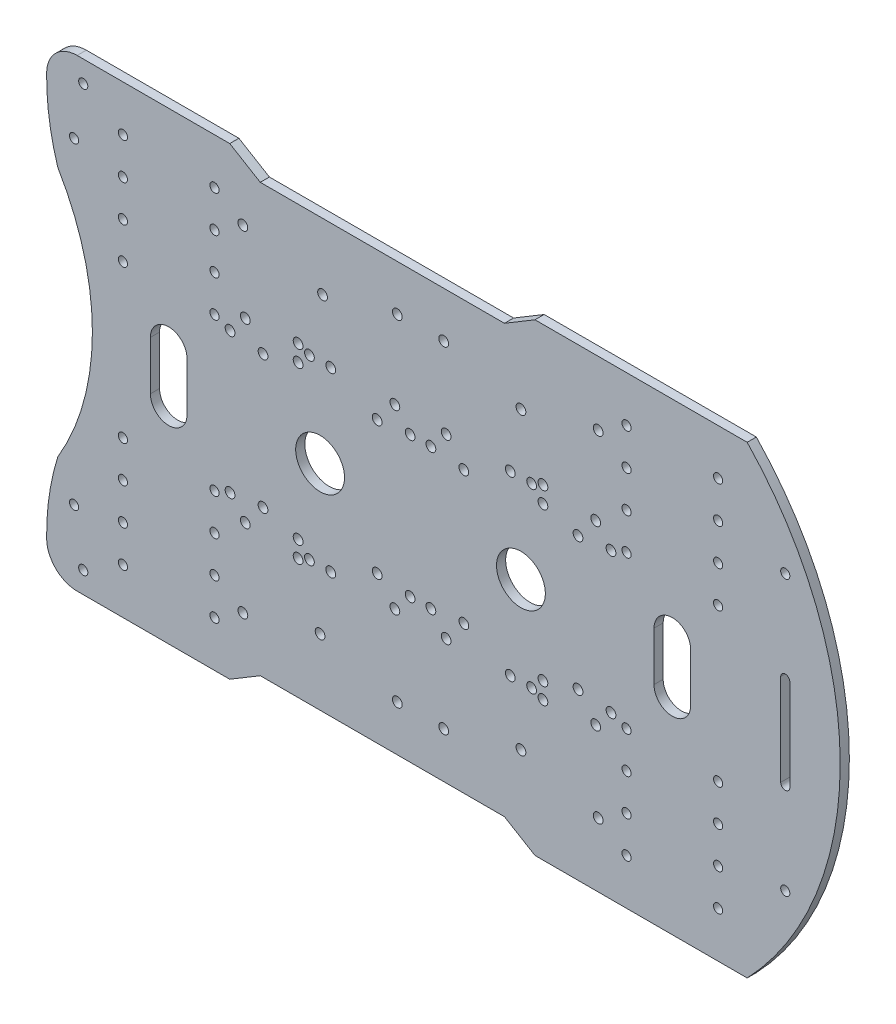
SolidWorks part; units mm, degrees
ref_plane "Front Plane" through (0, 0, 0) normal (0, 0, 1) x (1, 0, 0)
ref_plane "Top Plane" through (0, 0, 0) normal (0, 1, 0) x (1, 0, 0)
ref_plane "Right Plane" through (0, 0, 0) normal (1, 0, 0) x (0, 0, -1)
sketch "Model" plane through (0, 0, 0) normal (0, 0, 1) x (1, 0, 0)
  line L0 (404, 14.25) -> (584, 14.25)
  line L1 (584, 48.25) -> (404, 48.25)
  line L2 (404, 65.25) -> (584, 65.25)
  line L3 (430.991, 48.25) -> (430.991, 10)
  line L4 (502.8, 31.25) -> (404, 31.25)
  line L5 (502.8, 35.5) -> (404, 35.5)
  line L6 (502.8, 39.75) -> (404, 39.75)
  line L7 (502.8, 44) -> (404, 44)
  line L8 (458.6, 10) -> (458.6, 48.25)
  line L9 (404, 65.25) -> (404, 10)
  line L10 (411.8, 48.25) -> (411.8, 10)
  line L11 (437.8, 48.25) -> (437.8, 65.25)
  line L12 (448.3989, 48.25) -> (448.3989, 10)
  line L13 (469, 31.25) -> (469, 48.25)
  line L14 (458.6, 18.5) -> (404, 18.5)
  line L15 (484.6, 65.25) -> (484.6, 27)
  line L16 (458.6, 22.7499) -> (404, 22.7499)
  line L17 (458.6, 27) -> (404, 27)
  line L18 (458.6, 27) -> (584, 27)
  line L19 (502.8, 65.25) -> (502.8, 10)
  line L20 (547, 10) -> (547, 14.25)
  line L21 (554.8, 58.875) -> (554.8, 65.25)
  line L22 (571, 14.25) -> (571, 27)
  line L23 (584, 58.875) -> (502.8, 58.875)
  line L24 (584, 18.5) -> (571, 18.5)
  line L25 (20, 10) -> (20, 410)
  line L26 (20, 410) -> (584, 410)
  line L27 (584, 410) -> (584, 10)
  line L28 (584, 10) -> (20, 10)
  line L29 (15, 5) -> (15, 415)
  line L30 (15, 415) -> (589, 415)
  line L31 (589, 415) -> (589, 5)
  line L32 (589, 5) -> (15, 5)
  line L33 (15, 210) -> (25, 210)
  line L34 (302, 415) -> (302, 405)
  line L35 (589, 210) -> (579, 210)
  line L36 (302, 5) -> (302, 15)
  line L37 (20, 60) -> (15, 60)
  line L38 (584, 60) -> (589, 60)
  line L39 (20, 110) -> (15, 110)
  line L40 (584, 110) -> (589, 110)
  line L41 (20, 160) -> (15, 160)
  line L42 (584, 160) -> (589, 160)
  line L43 (20, 210) -> (15, 210)
  line L44 (584, 210) -> (589, 210)
  line L45 (20, 260) -> (15, 260)
  line L46 (584, 260) -> (589, 260)
  line L47 (20, 310) -> (15, 310)
  line L48 (584, 310) -> (589, 310)
  line L49 (20, 360) -> (15, 360)
  line L50 (584, 360) -> (589, 360)
  line L51 (52, 410) -> (52, 415)
  line L52 (52, 10) -> (52, 5)
  line L53 (102, 410) -> (102, 415)
  line L54 (102, 10) -> (102, 5)
  line L55 (152, 410) -> (152, 415)
  line L56 (152, 10) -> (152, 5)
  line L57 (202, 410) -> (202, 415)
  line L58 (202, 10) -> (202, 5)
  line L59 (252, 410) -> (252, 415)
  line L60 (252, 10) -> (252, 5)
  line L61 (302, 410) -> (302, 415)
  line L62 (302, 10) -> (302, 5)
  line L63 (352, 410) -> (352, 415)
  line L64 (352, 10) -> (352, 5)
  line L65 (402, 410) -> (402, 415)
  line L66 (402, 10) -> (402, 5)
  line L67 (452, 410) -> (452, 415)
  line L68 (452, 10) -> (452, 5)
  line L69 (502, 410) -> (502, 415)
  line L70 (502, 10) -> (502, 5)
  line L71 (552, 410) -> (552, 415)
  line L72 (552, 10) -> (552, 5)
  line L73 (307.6913, 297.7528) -> (307.6913, 281.7528)
  line L74 (319.6913, 297.7528) -> (319.6913, 281.7528)
  line L75 (349.1913, 304.7528) -> (349.1913, 274.7528)
  line L76 (352.1913, 304.7528) -> (352.1913, 274.7528)
  line L77 (142.6913, 297.7528) -> (142.6913, 281.7528)
  line L78 (154.6913, 297.7528) -> (154.6913, 281.7528)
  line L79 (118.6985, 365.7528) -> (168.6913, 365.7528)
  line L80 (168.6913, 365.7528) -> (178.6913, 359.7528)
  line L81 (178.6913, 359.7528) -> (258.6913, 359.7528)
  line L82 (258.6913, 359.7528) -> (268.6913, 365.7528)
  line L83 (268.6913, 365.7528) -> (338.2149, 365.7528)
  line L84 (268.6913, 213.7528) -> (338.2149, 213.7528)
  line L85 (258.6913, 219.7528) -> (268.6913, 213.7528)
  line L86 (178.6913, 219.7528) -> (258.6913, 219.7528)
  line L87 (168.6913, 213.7528) -> (178.6913, 219.7528)
  line L88 (118.6985, 213.7528) -> (168.6913, 213.7528)
  line L89 (473.3173, 213.7528) -> (473.3173, 365.7528)
  line L90 (473.3173, 365.7528) -> (476.3173, 365.7528)
  line L91 (473.3173, 213.7528) -> (476.3173, 213.7528)
  line L92 (476.3173, 365.7528) -> (476.3173, 213.7528)
  circle A0 centre (328.6913, 264.7528) radius 1.5
  circle A1 centre (298.6913, 252.7528) radius 1.5
  circle A2 centre (298.6913, 240.7528) radius 1.5
  circle A3 centre (298.6913, 228.7528) radius 1.5
  arc A4 (319.6913, 297.7528) -> (307.6913, 297.7528) centre (313.6913, 297.7528) ccw
  arc A5 (352.1913, 304.7528) -> (349.1913, 304.7528) centre (350.6913, 304.7528) ccw
  circle A6 centre (163.6913, 264.7528) radius 1.5
  circle A7 centre (163.6913, 252.7528) radius 1.5
  circle A8 centre (163.6913, 240.7528) radius 1.5
  circle A9 centre (163.6913, 228.7528) radius 1.5
  circle A10 centre (120.6913, 220.7528) radius 1.5
  arc A11 (154.6913, 297.7528) -> (142.6913, 297.7528) centre (148.6913, 297.7528) ccw
  circle A12 centre (163.6913, 314.7528) radius 1.5
  circle A13 centre (133.6913, 314.7528) radius 1.5
  circle A14 centre (163.6913, 326.7528) radius 1.5
  circle A15 centre (133.6913, 326.7528) radius 1.5
  circle A16 centre (163.6913, 338.7528) radius 1.5
  circle A17 centre (133.6913, 338.7528) radius 1.5
  circle A18 centre (163.6913, 350.7528) radius 1.5
  circle A19 centre (133.6913, 350.7528) radius 1.5
  circle A20 centre (120.6913, 358.7528) radius 1.5
  circle A21 centre (117.6913, 341.7528) radius 1.5
  circle A22 centre (298.6913, 314.7528) radius 1.5
  circle A23 centre (328.6913, 314.7528) radius 1.5
  circle A24 centre (328.6913, 326.7528) radius 1.5
  circle A25 centre (298.6913, 326.7528) radius 1.5
  circle A26 centre (328.6913, 338.7528) radius 1.5
  circle A27 centre (298.6913, 338.7528) radius 1.5
  circle A28 centre (328.6913, 350.7528) radius 1.5
  circle A29 centre (298.6913, 350.7528) radius 1.5
  circle A30 centre (350.6913, 334.7528) radius 1.5
  arc A31 (112.365, 248.717) -> (112.365, 330.7885) centre (43.6913, 289.7528) ccw
  circle A32 centre (117.6913, 237.7528) radius 1.5
  circle A33 centre (133.6913, 228.7528) radius 1.5
  circle A34 centre (133.6913, 240.7528) radius 1.5
  circle A35 centre (133.6913, 252.7528) radius 1.5
  circle A36 centre (133.6913, 264.7528) radius 1.5
  circle A37 centre (350.6913, 244.7528) radius 1.5
  circle A38 centre (328.6913, 228.7528) radius 1.5
  circle A39 centre (328.6913, 240.7528) radius 1.5
  circle A40 centre (328.6913, 252.7528) radius 1.5
  circle A41 centre (298.6913, 264.7528) radius 1.5
  arc A42 (307.6913, 281.7528) -> (319.6913, 281.7528) centre (313.6913, 281.7528) ccw
  arc A43 (349.1913, 274.7528) -> (352.1913, 274.7528) centre (350.6913, 274.7528) ccw
  arc A44 (142.6913, 281.7528) -> (154.6913, 281.7528) centre (148.6913, 281.7528) ccw
  arc A45 (108.6995, 355.8956) -> (112.365, 330.7885) centre (188.6913, 354.7528) ccw
  arc A46 (338.2149, 213.7528) -> (338.2149, 365.7528) centre (258.6913, 289.7528) ccw
  arc A47 (112.365, 248.717) -> (108.6995, 223.6099) centre (188.6913, 224.7528) ccw
  arc A48 (118.6985, 365.7528) -> (108.6995, 355.8956) centre (118.6985, 355.7528) ccw
  arc A49 (108.6995, 223.6099) -> (118.6985, 213.7528) centre (118.6985, 223.7528) ccw
  circle A50 centre (288.5913, 260.7528) radius 1.6
  circle A51 centre (239.5913, 260.7528) radius 1.6
  circle A52 centre (264.0913, 289.7528) radius 8
  circle A53 centre (245.3913, 267.9528) radius 1.6
  circle A54 centre (293.5913, 266.7528) radius 1.6
  circle A55 centre (234.5913, 266.7528) radius 1.6
  circle A56 centre (282.7913, 267.9528) radius 1.6
  circle A57 centre (260.5913, 260.7528) radius 1.6
  circle A58 centre (267.5913, 260.7528) radius 1.6
  circle A59 centre (289.3913, 344.7528) radius 1.6
  circle A60 centre (238.7913, 234.7528) radius 1.6
  circle A61 centre (289.3913, 234.7528) radius 1.6
  circle A62 centre (288.5913, 318.7528) radius 1.6
  circle A63 centre (239.5913, 318.7528) radius 1.6
  circle A64 centre (245.3913, 311.5528) radius 1.6
  circle A65 centre (293.5913, 312.7528) radius 1.6
  circle A66 centre (234.5913, 312.7528) radius 1.6
  circle A67 centre (282.7913, 311.5528) radius 1.6
  circle A68 centre (260.5913, 318.7528) radius 1.6
  circle A69 centre (267.5913, 318.7528) radius 1.6
  circle A70 centre (264.0913, 338.0528) radius 1.6
  circle A71 centre (264.0913, 241.4528) radius 1.6
  circle A72 centre (191.0913, 264.6528) radius 1.6
  circle A73 centre (191.0913, 259.2528) radius 1.6
  circle A74 centre (191.0913, 314.8528) radius 1.6
  circle A75 centre (191.0913, 320.2528) radius 1.6
  circle A76 centre (271.2913, 314.8528) radius 1.6
  circle A77 centre (271.2913, 320.2528) radius 1.6
  circle A78 centre (271.2913, 264.6528) radius 1.6
  circle A79 centre (271.2913, 259.2528) radius 1.6
  circle A80 centre (222.7913, 260.7528) radius 1.6
  circle A81 centre (173.7913, 260.7528) radius 1.6
  circle A82 centre (198.2913, 289.7528) radius 8
  circle A83 centre (179.5913, 267.9528) radius 1.6
  circle A84 centre (227.7913, 266.7528) radius 1.6
  circle A85 centre (168.7913, 266.7528) radius 1.6
  circle A86 centre (216.9913, 267.9528) radius 1.6
  circle A87 centre (194.7913, 260.7528) radius 1.6
  circle A88 centre (201.7913, 260.7528) radius 1.6
  circle A89 centre (172.9913, 344.7528) radius 1.6
  circle A90 centre (223.5913, 344.7528) radius 1.6
  circle A91 centre (172.9913, 234.7528) radius 1.6
  circle A92 centre (223.5913, 234.7528) radius 1.6
  circle A93 centre (222.7913, 318.7528) radius 1.6
  circle A94 centre (173.7913, 318.7528) radius 1.6
  circle A95 centre (179.5913, 311.5528) radius 1.6
  circle A96 centre (227.7913, 312.7528) radius 1.6
  circle A97 centre (168.7913, 312.7528) radius 1.6
  circle A98 centre (216.9913, 311.5528) radius 1.6
  circle A99 centre (194.7913, 318.7528) radius 1.6
  circle A100 centre (201.7913, 318.7528) radius 1.6
  circle A101 centre (199.1008, 338.0528) radius 1.6
  circle A102 centre (198.2913, 241.4528) radius 1.6
  circle A103 centre (238.7913, 344.7528) radius 1.6
  text T0 "除非另外指定:" font "SWTXT" height 1.5
  text T1 "尺寸使用毫米" font "SWTXT" height 1.5
  text T2 "表面粗糙度:" font "SWTXT" height 1.5
  text T3 "公差:" font "SWTXT" height 1.5
  text T4 "线性:" font "SWTXT" height 1.5
  text T5 "角度:" font "SWTXT" height 1.5
  text T6 "将锐边清除" font "SWTXT" height 1.5
  text T7 "毛刺并折断" font "SWTXT" height 1.5
  text T8 "A" font "SWTXT" height 3.9688
  text T9 "A" font "SWTXT" height 3.9688
  text T10 "B" font "SWTXT" height 3.9688
  text T11 "B" font "SWTXT" height 3.9688
  text T12 "C" font "SWTXT" height 3.9688
  text T13 "C" font "SWTXT" height 3.9688
  text T14 "D" font "SWTXT" height 3.9688
  text T15 "D" font "SWTXT" height 3.9688
  text T16 "E" font "SWTXT" height 3.9688
  text T17 "E" font "SWTXT" height 3.9688
  text T18 "F" font "SWTXT" height 3.9688
  text T19 "F" font "SWTXT" height 3.9688
  text T20 "G" font "SWTXT" height 3.9688
  text T21 "G" font "SWTXT" height 3.9688
  text T22 "H" font "SWTXT" height 3.9688
  text T23 "H" font "SWTXT" height 3.9688
  text T24 "12" font "SWTXT" height 3.9688
  text T25 "12" font "SWTXT" height 3.9688
  text T26 "11" font "SWTXT" height 3.9688
  text T27 "11" font "SWTXT" height 3.9688
  text T28 "10" font "SWTXT" height 3.9688
  text T29 "10" font "SWTXT" height 3.9688
  text T30 "9" font "SWTXT" height 3.9688
  text T31 "9" font "SWTXT" height 3.9688
  text T32 "8" font "SWTXT" height 3.9688
  text T33 "8" font "SWTXT" height 3.9688
  text T34 "7" font "SWTXT" height 3.9688
  text T35 "7" font "SWTXT" height 3.9688
  text T36 "6" font "SWTXT" height 3.9688
  text T37 "6" font "SWTXT" height 3.9688
  text T38 "5" font "SWTXT" height 3.9688
  text T39 "5" font "SWTXT" height 3.9688
  text T40 "4" font "SWTXT" height 3.9688
  text T41 "4" font "SWTXT" height 3.9688
  text T42 "3" font "SWTXT" height 3.9688
  text T43 "3" font "SWTXT" height 3.9688
  text T44 "2" font "SWTXT" height 3.9688
  text T45 "2" font "SWTXT" height 3.9688
  text T46 "1" font "SWTXT" height 3.9688
  text T47 "1" font "SWTXT" height 3.9688
  text T48 "绘制" font "SWTXT" height 1.5
  text T49 "检查" font "SWTXT" height 1.5
  text T50 "批准" font "SWTXT" height 1.5
  text T51 "制造" font "SWTXT" height 1.5
  text T52 "验检" font "SWTXT" height 1.5
  text T53 "表面粗糙度:" font "SWTXT" height 1.5
  text T54 "名称" font "SWTXT" height 1.5
  text T55 "签名" font "SWTXT" height 1.5
  text T56 "日期" font "SWTXT" height 1.5
  text T57 "材料:" font "SWTXT" height 1.5
  text T58 "不调整工程图比例" font "SWTXT" height 1.5
  text T59 "修订" font "SWTXT" height 1.5
  text T60 "标题:" font "SWTXT" height 1.5
  text T61 "工程图号" font "SWTXT" height 1.5
  text T62 "比例:1:1" font "SWTXT" height 1.5
  text T63 "图纸 1 (共1)" font "SWTXT" height 1.5
  text T64 "A2" font "SWTXT" height 2.9104
  text T65 "材质 <未指定>" font "SWTXT" height 2.3812
  text T66 "重量: 0.101" font "SWTXT" height 1.4986
  text T67 "底盘A" font "SWTXT" height 6.35
sketch "Sketch2" plane through (0, 0, 0) normal (0, 0, 1) x (1, 0, 0)
  line L0 (118.6985, 213.7528) -> (168.6913, 213.7528) construction
  line L1 (168.6913, 213.7528) -> (178.6913, 219.7528) construction
  line L2 (178.6913, 219.7528) -> (258.6913, 219.7528) construction
  line L3 (258.6913, 219.7528) -> (268.6913, 213.7528) construction
  line L4 (268.6913, 213.7528) -> (338.2149, 213.7528) construction
  line L5 (268.6913, 365.7528) -> (338.2149, 365.7528) construction
  line L6 (258.6913, 359.7528) -> (268.6913, 365.7528) construction
  line L7 (178.6913, 359.7528) -> (258.6913, 359.7528) construction
  line L8 (168.6913, 365.7528) -> (178.6913, 359.7528) construction
  line L9 (118.6985, 365.7528) -> (168.6913, 365.7528) construction
  line L10 (118.6985, 213.7528) -> (168.6913, 213.7528)
  line L11 (168.6913, 213.7528) -> (178.6913, 219.7528)
  line L12 (178.6913, 219.7528) -> (258.6913, 219.7528)
  line L13 (258.6913, 219.7528) -> (268.6913, 213.7528)
  line L14 (268.6913, 213.7528) -> (338.2149, 213.7528)
  line L15 (268.6913, 365.7528) -> (338.2149, 365.7528)
  line L16 (258.6913, 359.7528) -> (268.6913, 365.7528)
  line L17 (178.6913, 359.7528) -> (258.6913, 359.7528)
  line L18 (168.6913, 365.7528) -> (178.6913, 359.7528)
  line L19 (118.6985, 365.7528) -> (168.6913, 365.7528)
  line L20 (142.6913, 297.7528) -> (142.6913, 281.7528) construction
  line L21 (154.6913, 297.7528) -> (154.6913, 281.7528) construction
  line L22 (142.6913, 297.7528) -> (142.6913, 281.7528)
  line L23 (154.6913, 297.7528) -> (154.6913, 281.7528)
  line L24 (307.6913, 297.7528) -> (307.6913, 281.7528) construction
  line L25 (319.6913, 297.7528) -> (319.6913, 281.7528) construction
  line L26 (307.6913, 297.7528) -> (307.6913, 281.7528)
  line L27 (319.6913, 297.7528) -> (319.6913, 281.7528)
  line L28 (349.1913, 304.7528) -> (349.1913, 274.7528) construction
  line L29 (352.1913, 304.7528) -> (352.1913, 274.7528) construction
  line L30 (349.1913, 304.7528) -> (349.1913, 274.7528)
  line L31 (352.1913, 304.7528) -> (352.1913, 274.7528)
  arc A0 (112.365, 248.717) -> (108.6995, 223.6099) centre (188.6913, 224.7528) ccw construction
  arc A1 (108.6995, 223.6099) -> (118.6985, 213.7528) centre (118.6985, 223.7528) ccw construction
  arc A2 (338.2149, 213.7528) -> (338.2149, 365.7528) centre (258.6913, 289.7528) ccw construction
  arc A3 (118.6985, 365.7528) -> (108.6995, 355.8956) centre (118.6985, 355.7528) ccw construction
  arc A4 (108.6995, 355.8956) -> (112.365, 330.7885) centre (188.6913, 354.7528) ccw construction
  arc A5 (112.365, 248.717) -> (112.365, 330.7885) centre (43.6913, 289.7528) ccw construction
  arc A6 (112.365, 248.717) -> (108.6995, 223.6099) centre (188.6913, 224.7528) ccw
  arc A7 (108.6995, 223.6099) -> (118.6985, 213.7528) centre (118.6985, 223.7528) ccw
  arc A8 (338.2149, 213.7528) -> (338.2149, 365.7528) centre (258.6913, 289.7528) ccw
  arc A9 (118.6985, 365.7528) -> (108.6995, 355.8956) centre (118.6985, 355.7528) ccw
  arc A10 (108.6995, 355.8956) -> (112.365, 330.7885) centre (188.6913, 354.7528) ccw
  arc A11 (112.365, 248.717) -> (112.365, 330.7885) centre (43.6913, 289.7528) ccw
  arc A12 (154.6913, 297.7528) -> (142.6913, 297.7528) centre (148.6913, 297.7528) ccw construction
  arc A13 (142.6913, 281.7528) -> (154.6913, 281.7528) centre (148.6913, 281.7528) ccw construction
  arc A14 (154.6913, 297.7528) -> (142.6913, 297.7528) centre (148.6913, 297.7528) ccw
  arc A15 (142.6913, 281.7528) -> (154.6913, 281.7528) centre (148.6913, 281.7528) ccw
  circle A16 centre (198.2913, 289.7528) radius 8 construction
  circle A17 centre (198.2913, 289.7528) radius 8
  circle A18 centre (264.0913, 289.7528) radius 8 construction
  circle A19 centre (264.0913, 289.7528) radius 8
  arc A20 (319.6913, 297.7528) -> (307.6913, 297.7528) centre (313.6913, 297.7528) ccw construction
  arc A21 (307.6913, 281.7528) -> (319.6913, 281.7528) centre (313.6913, 281.7528) ccw construction
  arc A22 (319.6913, 297.7528) -> (307.6913, 297.7528) centre (313.6913, 297.7528) ccw
  arc A23 (307.6913, 281.7528) -> (319.6913, 281.7528) centre (313.6913, 281.7528) ccw
  arc A24 (352.1913, 304.7528) -> (349.1913, 304.7528) centre (350.6913, 304.7528) ccw construction
  arc A25 (349.1913, 274.7528) -> (352.1913, 274.7528) centre (350.6913, 274.7528) ccw construction
  arc A26 (352.1913, 304.7528) -> (349.1913, 304.7528) centre (350.6913, 304.7528) ccw
  arc A27 (349.1913, 274.7528) -> (352.1913, 274.7528) centre (350.6913, 274.7528) ccw
  circle A28 centre (264.0913, 338.0528) radius 1.6 construction
  circle A29 centre (260.5913, 318.7528) radius 1.6 construction
  circle A30 centre (245.3913, 311.5528) radius 1.6 construction
  circle A31 centre (238.7913, 344.7528) radius 1.6 construction
  circle A32 centre (239.5913, 318.7528) radius 1.6 construction
  circle A33 centre (234.5913, 312.7528) radius 1.6 construction
  circle A34 centre (227.7913, 312.7528) radius 1.6 construction
  circle A35 centre (216.9913, 311.5528) radius 1.6 construction
  circle A36 centre (222.7913, 318.7528) radius 1.6 construction
  circle A37 centre (223.5913, 344.7528) radius 1.6 construction
  circle A38 centre (201.7913, 318.7528) radius 1.6 construction
  circle A39 centre (194.7913, 318.7528) radius 1.6 construction
  circle A40 centre (199.1008, 338.0528) radius 1.6 construction
  circle A41 centre (191.0913, 320.2528) radius 1.6 construction
  circle A42 centre (191.0913, 314.8528) radius 1.6 construction
  circle A43 centre (179.5913, 311.5528) radius 1.6 construction
  circle A44 centre (173.7913, 318.7528) radius 1.6 construction
  circle A45 centre (168.7913, 312.7528) radius 1.6 construction
  circle A46 centre (163.6913, 314.7528) radius 1.5 construction
  circle A47 centre (163.6913, 326.7528) radius 1.5 construction
  circle A48 centre (163.6913, 338.7528) radius 1.5 construction
  circle A49 centre (172.9913, 344.7528) radius 1.6 construction
  circle A50 centre (163.6913, 350.7528) radius 1.5 construction
  circle A51 centre (133.6913, 350.7528) radius 1.5 construction
  circle A52 centre (120.6913, 358.7528) radius 1.5 construction
  circle A53 centre (117.6913, 341.7528) radius 1.5 construction
  circle A54 centre (133.6913, 338.7528) radius 1.5 construction
  circle A55 centre (133.6913, 326.7528) radius 1.5 construction
  circle A56 centre (133.6913, 314.7528) radius 1.5 construction
  circle A57 centre (264.0913, 338.0528) radius 1.6
  circle A58 centre (260.5913, 318.7528) radius 1.6
  circle A59 centre (245.3913, 311.5528) radius 1.6
  circle A60 centre (238.7913, 344.7528) radius 1.6
  circle A61 centre (239.5913, 318.7528) radius 1.6
  circle A62 centre (234.5913, 312.7528) radius 1.6
  circle A63 centre (227.7913, 312.7528) radius 1.6
  circle A64 centre (216.9913, 311.5528) radius 1.6
  circle A65 centre (222.7913, 318.7528) radius 1.6
  circle A66 centre (223.5913, 344.7528) radius 1.6
  circle A67 centre (201.7913, 318.7528) radius 1.6
  circle A68 centre (194.7913, 318.7528) radius 1.6
  circle A69 centre (199.1008, 338.0528) radius 1.6
  circle A70 centre (191.0913, 320.2528) radius 1.6
  circle A71 centre (191.0913, 314.8528) radius 1.6
  circle A72 centre (179.5913, 311.5528) radius 1.6
  circle A73 centre (173.7913, 318.7528) radius 1.6
  circle A74 centre (168.7913, 312.7528) radius 1.6
  circle A75 centre (163.6913, 314.7528) radius 1.5
  circle A76 centre (163.6913, 326.7528) radius 1.5
  circle A77 centre (163.6913, 338.7528) radius 1.5
  circle A78 centre (172.9913, 344.7528) radius 1.6
  circle A79 centre (163.6913, 350.7528) radius 1.5
  circle A80 centre (133.6913, 350.7528) radius 1.5
  circle A81 centre (120.6913, 358.7528) radius 1.5
  circle A82 centre (117.6913, 341.7528) radius 1.5
  circle A83 centre (133.6913, 338.7528) radius 1.5
  circle A84 centre (133.6913, 326.7528) radius 1.5
  circle A85 centre (133.6913, 314.7528) radius 1.5
  circle A86 centre (198.2913, 241.4528) radius 1.6 construction
  circle A87 centre (201.7913, 260.7528) radius 1.6 construction
  circle A88 centre (216.9913, 267.9528) radius 1.6 construction
  circle A89 centre (227.7913, 266.7528) radius 1.6 construction
  circle A90 centre (222.7913, 260.7528) radius 1.6 construction
  circle A91 centre (223.5913, 234.7528) radius 1.6 construction
  circle A92 centre (238.7913, 234.7528) radius 1.6 construction
  circle A93 centre (234.5913, 266.7528) radius 1.6 construction
  circle A94 centre (245.3913, 267.9528) radius 1.6 construction
  circle A95 centre (239.5913, 260.7528) radius 1.6 construction
  circle A96 centre (264.0913, 241.4528) radius 1.6 construction
  circle A97 centre (260.5913, 260.7528) radius 1.6 construction
  circle A98 centre (267.5913, 260.7528) radius 1.6 construction
  circle A99 centre (271.2913, 264.6528) radius 1.6 construction
  circle A100 centre (271.2913, 259.2528) radius 1.6 construction
  circle A101 centre (289.3913, 234.7528) radius 1.6 construction
  circle A102 centre (298.6913, 228.7528) radius 1.5 construction
  circle A103 centre (298.6913, 240.7528) radius 1.5 construction
  circle A104 centre (288.5913, 260.7528) radius 1.6 construction
  circle A105 centre (282.7913, 267.9528) radius 1.6 construction
  circle A106 centre (293.5913, 266.7528) radius 1.6 construction
  circle A107 centre (298.6913, 264.7528) radius 1.5 construction
  circle A108 centre (298.6913, 252.7528) radius 1.5 construction
  circle A109 centre (328.6913, 228.7528) radius 1.5 construction
  circle A110 centre (328.6913, 240.7528) radius 1.5 construction
  circle A111 centre (328.6913, 252.7528) radius 1.5 construction
  circle A112 centre (328.6913, 264.7528) radius 1.5 construction
  circle A113 centre (350.6913, 244.7528) radius 1.5 construction
  circle A114 centre (350.6913, 334.7528) radius 1.5 construction
  circle A115 centre (328.6913, 350.7528) radius 1.5 construction
  circle A116 centre (328.6913, 338.7528) radius 1.5 construction
  circle A117 centre (328.6913, 326.7528) radius 1.5 construction
  circle A118 centre (328.6913, 314.7528) radius 1.5 construction
  circle A119 centre (282.7913, 311.5528) radius 1.6 construction
  circle A120 centre (288.5913, 318.7528) radius 1.6 construction
  circle A121 centre (293.5913, 312.7528) radius 1.6 construction
  circle A122 centre (298.6913, 314.7528) radius 1.5 construction
  circle A123 centre (298.6913, 326.7528) radius 1.5 construction
  circle A124 centre (298.6913, 338.7528) radius 1.5 construction
  circle A125 centre (298.6913, 350.7528) radius 1.5 construction
  circle A126 centre (289.3913, 344.7528) radius 1.6 construction
  circle A127 centre (271.2913, 320.2528) radius 1.6 construction
  circle A128 centre (271.2913, 314.8528) radius 1.6 construction
  circle A129 centre (267.5913, 318.7528) radius 1.6 construction
  circle A130 centre (198.2913, 241.4528) radius 1.6
  circle A131 centre (201.7913, 260.7528) radius 1.6
  circle A132 centre (216.9913, 267.9528) radius 1.6
  circle A133 centre (227.7913, 266.7528) radius 1.6
  circle A134 centre (222.7913, 260.7528) radius 1.6
  circle A135 centre (223.5913, 234.7528) radius 1.6
  circle A136 centre (238.7913, 234.7528) radius 1.6
  circle A137 centre (234.5913, 266.7528) radius 1.6
  circle A138 centre (245.3913, 267.9528) radius 1.6
  circle A139 centre (239.5913, 260.7528) radius 1.6
  circle A140 centre (264.0913, 241.4528) radius 1.6
  circle A141 centre (260.5913, 260.7528) radius 1.6
  circle A142 centre (267.5913, 260.7528) radius 1.6
  circle A143 centre (271.2913, 264.6528) radius 1.6
  circle A144 centre (271.2913, 259.2528) radius 1.6
  circle A145 centre (289.3913, 234.7528) radius 1.6
  circle A146 centre (298.6913, 228.7528) radius 1.5
  circle A147 centre (298.6913, 240.7528) radius 1.5
  circle A148 centre (288.5913, 260.7528) radius 1.6
  circle A149 centre (282.7913, 267.9528) radius 1.6
  circle A150 centre (293.5913, 266.7528) radius 1.6
  circle A151 centre (298.6913, 264.7528) radius 1.5
  circle A152 centre (298.6913, 252.7528) radius 1.5
  circle A153 centre (328.6913, 228.7528) radius 1.5
  circle A154 centre (328.6913, 240.7528) radius 1.5
  circle A155 centre (328.6913, 252.7528) radius 1.5
  circle A156 centre (328.6913, 264.7528) radius 1.5
  circle A157 centre (350.6913, 244.7528) radius 1.5
  circle A158 centre (350.6913, 334.7528) radius 1.5
  circle A159 centre (328.6913, 350.7528) radius 1.5
  circle A160 centre (328.6913, 338.7528) radius 1.5
  circle A161 centre (328.6913, 326.7528) radius 1.5
  circle A162 centre (328.6913, 314.7528) radius 1.5
  circle A163 centre (282.7913, 311.5528) radius 1.6
  circle A164 centre (288.5913, 318.7528) radius 1.6
  circle A165 centre (293.5913, 312.7528) radius 1.6
  circle A166 centre (298.6913, 314.7528) radius 1.5
  circle A167 centre (298.6913, 326.7528) radius 1.5
  circle A168 centre (298.6913, 338.7528) radius 1.5
  circle A169 centre (298.6913, 350.7528) radius 1.5
  circle A170 centre (289.3913, 344.7528) radius 1.6
  circle A171 centre (271.2913, 320.2528) radius 1.6
  circle A172 centre (271.2913, 314.8528) radius 1.6
  circle A173 centre (267.5913, 318.7528) radius 1.6
  circle A174 centre (120.6913, 220.7528) radius 1.5 construction
  circle A175 centre (117.6913, 237.7528) radius 1.5 construction
  circle A176 centre (133.6913, 264.7528) radius 1.5 construction
  circle A177 centre (133.6913, 252.7528) radius 1.5 construction
  circle A178 centre (133.6913, 240.7528) radius 1.5 construction
  circle A179 centre (133.6913, 228.7528) radius 1.5 construction
  circle A180 centre (163.6913, 228.7528) radius 1.5 construction
  circle A181 centre (163.6913, 240.7528) radius 1.5 construction
  circle A182 centre (172.9913, 234.7528) radius 1.6 construction
  circle A183 centre (163.6913, 252.7528) radius 1.5 construction
  circle A184 centre (163.6913, 264.7528) radius 1.5 construction
  circle A185 centre (168.7913, 266.7528) radius 1.6 construction
  circle A186 centre (173.7913, 260.7528) radius 1.6 construction
  circle A187 centre (179.5913, 267.9528) radius 1.6 construction
  circle A188 centre (191.0913, 264.6528) radius 1.6 construction
  circle A189 centre (194.7913, 260.7528) radius 1.6 construction
  circle A190 centre (191.0913, 259.2528) radius 1.6 construction
  circle A191 centre (120.6913, 220.7528) radius 1.5
  circle A192 centre (117.6913, 237.7528) radius 1.5
  circle A193 centre (133.6913, 264.7528) radius 1.5
  circle A194 centre (133.6913, 252.7528) radius 1.5
  circle A195 centre (133.6913, 240.7528) radius 1.5
  circle A196 centre (133.6913, 228.7528) radius 1.5
  circle A197 centre (163.6913, 228.7528) radius 1.5
  circle A198 centre (163.6913, 240.7528) radius 1.5
  circle A199 centre (172.9913, 234.7528) radius 1.6
  circle A200 centre (163.6913, 252.7528) radius 1.5
  circle A201 centre (163.6913, 264.7528) radius 1.5
  circle A202 centre (168.7913, 266.7528) radius 1.6
  circle A203 centre (173.7913, 260.7528) radius 1.6
  circle A204 centre (179.5913, 267.9528) radius 1.6
  circle A205 centre (191.0913, 264.6528) radius 1.6
  circle A206 centre (194.7913, 260.7528) radius 1.6
  circle A207 centre (191.0913, 259.2528) radius 1.6
extrude "Boss-Extrude1" add sketch "Sketch2" along normal blind 3
